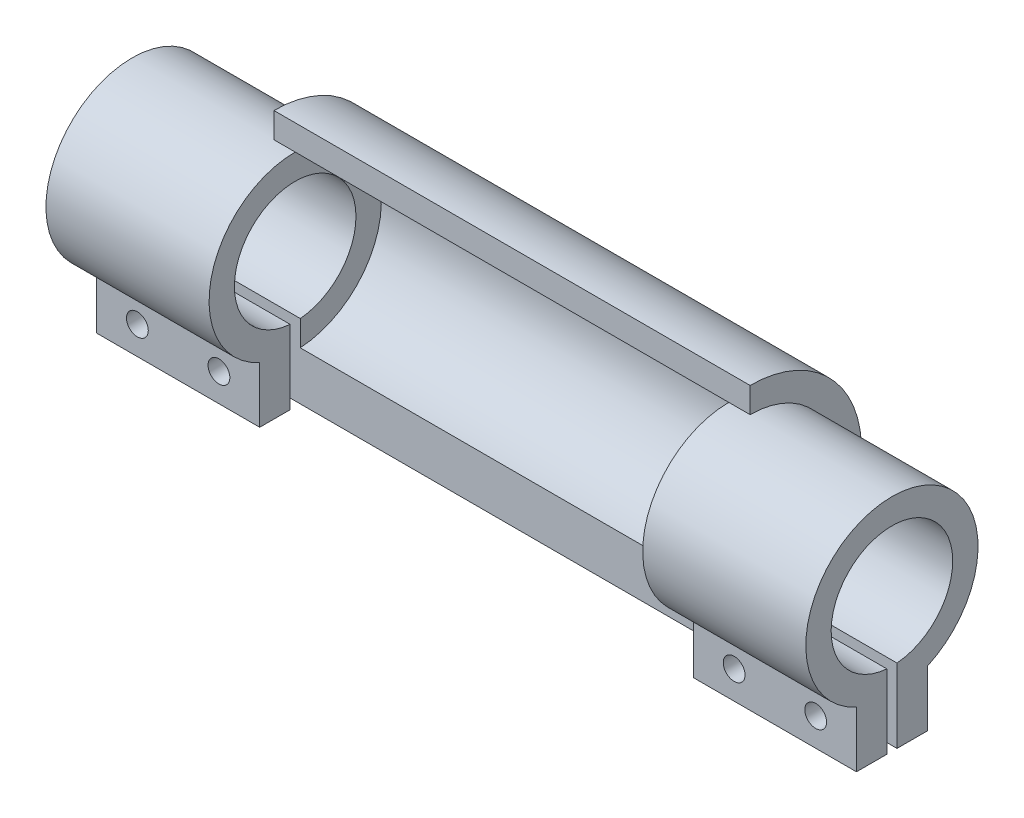
SolidWorks part; units mm, degrees
material "PLA Black"
ref_plane "Front" through (0, 0, 0) normal (0, 0, 1) x (1, 0, 0)
ref_plane "Top" through (0, 0, 0) normal (0, 1, 0) x (1, 0, 0)
ref_plane "Right" through (0, 0, 0) normal (1, 0, 0) x (0, 0, -1)
sketch "Sketch2" plane through (0, 0, 0) normal (1, 0, 0) x (0, 0, -1)
  line L0 (0, 23.2189) -> (0, -23.7979) construction
  line L1 (1, -11.9583) -> (1, -26.5583)
  line L2 (1, -26.5583) -> (7, -26.5583)
  line L3 (7, -26.5583) -> (7, -15.4919)
  line L4 (-1, -26.5583) -> (-7, -26.5583)
  line L5 (-7, -26.5583) -> (-7, -15.4919)
  line L6 (-1, -11.9583) -> (-1, -26.5583)
  line L7 (-19.1554, -19.2583) -> (23.3552, -19.2583) construction
  circle A0 centre (0, 0) radius 11 construction
  arc A1 (-1, -11.9583) -> (1, -11.9583) centre (0, 0) cw
  arc A2 (7, -15.4919) -> (-7, -15.4919) centre (0, 0) ccw
  dimension "D1" = 22
  dimension "D2" = 1
  dimension "D3" = 5
  dimension "D4" = 7.3
  dimension "D5" = 2
  dimension "D6" = 6
extrude "Boss-Extrude1" add sketch "Sketch2" along normal mid plane 150
sketch "Sketch3" plane through (0, 0, 0) normal (0, 0, 1) x (1, 0, 0)
  line L1 (-42.8, 17) -> (42.8, 17)
  line L2 (-42.8, 17) -> (-42.8, -26.5583)
  line L3 (-42.8, -26.5583) -> (42.8, -26.5583)
  line L4 (42.8, 17) -> (42.8, -26.5583)
  line L5 (0, 40.6836) -> (0, -52.0926) construction
  line L6 (75, -26.5583) -> (-75, -26.5583) construction
  line L7 (75, -15.4919) -> (75, -26.5583) construction
  line L8 (75, 17) -> (-75, 17) construction
  dimension "D1" = 32.2
extrude "Cut-Extrude1" cut sketch "Sketch3" against normal through all both and the other way through all
sketch "Sketch4" plane through (0, 0, 7) normal (0, 0, 1) x (1, 0, 0)
  line L0 (58.9, 28.0903) -> (58.9, -42.3686) construction
  line L1 (42.8, -15.4919) -> (42.8, -26.5583) construction
  line L2 (75, -15.4919) -> (75, -26.5583) construction
  line L3 (0, 23.4284) -> (0, -33.4917) construction
  line L4 (42.8, -21.0251) -> (58.9, -21.0251) construction
  circle A0 centre (50.85, -21.0251) radius 2.15
  circle A1 centre (66.95, -21.0251) radius 2.15
  circle A2 centre (-50.85, -21.0251) radius 2.15
  circle A3 centre (-66.95, -21.0251) radius 2.15
  dimension "D1" = 4.3
extrude "Cut-Extrude2" cut sketch "Sketch4" against normal up to next (6 mm away)
hole_wizard "M3 Clearance Hole1" positions "Sketch6" profile "Sketch5" hole size "M3" standard "DIN" end condition through all
sketch "Sketch6" plane through (0, 0, -7) normal (0, 0, -1) x (-1, 0, 0)
  circle A2 centre (50.85, -21.0251) radius 2.15 construction
  circle A3 centre (66.95, -21.0251) radius 2.15 construction
  point P0 (-66.95, -20.7964)
  point P2 (-50.85, -20.7964)
  point P4 (50.85, -21.0251)
  point P6 (66.95, -21.0251)
sketch "Sketch5" plane through (66.95, -20.7964, -7) normal (1, 0, 0) x (0, 1, 0)
  line L0 (0, 0) -> (0, 24)
  line L1 (0, 24) -> (1.7, 24)
  line L2 (1.7, 24) -> (1.7, 0)
  line L5 (1.7, 0) -> (0, 0)
  line L11 (0, -6.35) -> (0, 107.95) construction
  dimension "Thru Hole Dia." = 3.4
  dimension "Thru Hole Depth" = 24
sketch "Sketch8" plane through (0, 0, 0) normal (1, 0, 0) x (0, 0, -1)
  line L0 (0, 17) -> (0, 22)
  line L1 (1, -16.9706) -> (1, -26.5583)
  line L2 (1, -11.9583) -> (1, -26.5583) construction
  line L3 (7, -26.5583) -> (1, -26.5583) construction
  line L4 (1, -26.5583) -> (7, -26.5583)
  line L5 (7, -26.5583) -> (7, -20.8567)
  line L6 (7, -15.4919) -> (7, -26.5583) construction
  arc A0 (0, 22) -> (7, -20.8567) centre (0, 0) cw
  arc A1 (0, 17) -> (1, -16.9706) centre (0, 0) cw
  arc A3 (7, -15.4919) -> (-7, -15.4919) centre (0, 0) ccw construction
  dimension "D1" = 5
extrude "Boss-Extrude2" add sketch "Sketch8" along normal blind 47 and the other way blind 47
